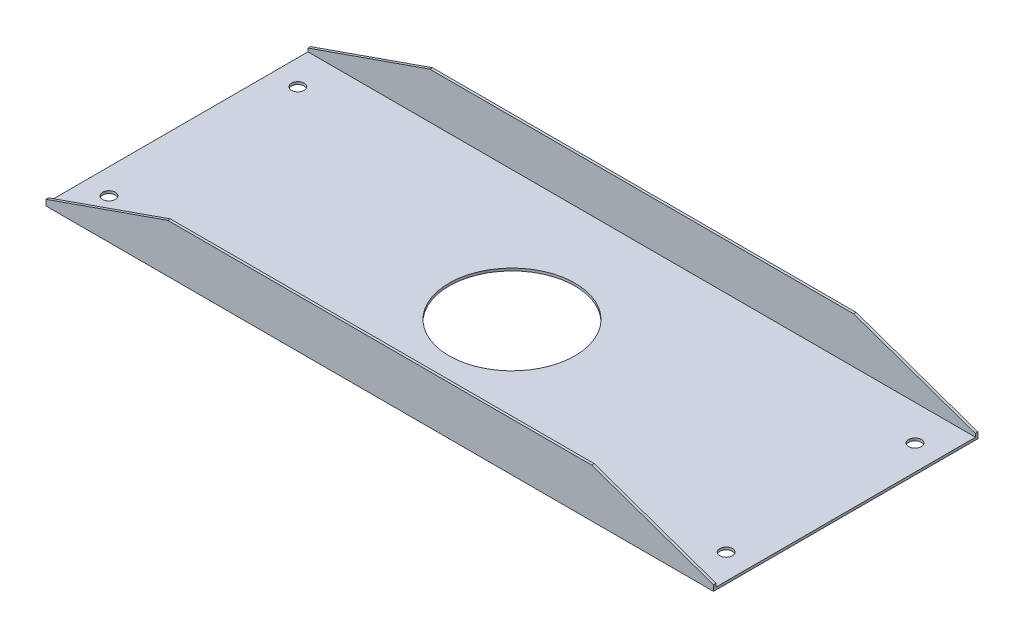
SolidWorks part; units mm, degrees
ref_plane "Спереди" through (0, 0, 0) normal (0, 0, 1) x (1, 0, 0)
ref_plane "Сверху" through (0, 0, 0) normal (0, 1, 0) x (1, 0, 0)
ref_plane "Справа" through (0, 0, 0) normal (1, 0, 0) x (0, 0, -1)
sketch "Эскиз1" plane through (0, 0, 0) normal (1, 0, 0) x (0, 0, -1)
  line L0 (-105, 0) -> (105, 0)
  line L1 (105, 0) -> (105, 38.5)
  line L2 (-105, 0) -> (-105, 38.5)
  dimension "D1" = 210
  dimension "D2" = 38.5
  dimension "D3" = 38.5
extrude "Вытянуть-Тонкостенный1" add sketch "Эскиз1" along normal blind 530 thin thin type one direction wall 2
sketch "Эскиз2" plane through (0, 0, -105) normal (0, 0, -1) x (-1, 0, 0)
  line L0 (-530, 0) -> (-530, 4.6148)
  line L1 (-530, 38.5) -> (-530, 0) construction
  line L2 (-530, 4.6148) -> (-433.2757, 38.5)
  line L3 (-530, 38.5) -> (0, 38.5) construction
  line L4 (-433.2757, 38.5) -> (-96.7243, 38.5)
  line L5 (-96.7243, 38.5) -> (0, 4.6148)
  line L6 (0, 38.5) -> (0, 0) construction
  line L7 (0, 4.6148) -> (0, 0)
  line L8 (0, 0) -> (-530, 0)
extrude "Вырез-Вытянуть2" cut sketch "Эскиз2" against normal through all flip side to cut
sketch "Эскиз3" plane through (0, 2, 0) normal (0, 1, 0) x (1, 0, 0)
  line L0 (20, 115.302) -> (20, -116.3672) construction
  line L1 (0, 103) -> (0, -103) construction
  line L2 (0, 105) -> (96.7243, 105) construction
  line L3 (510, 126.018) -> (510, -161.4271) construction
  line L4 (530, 103) -> (530, -103) construction
  line L5 (0, 103) -> (530, -103) construction
  line L6 (530, 103) -> (0, -103) construction
  circle A0 centre (20, 75) radius 5
  circle A1 centre (20, -75) radius 5
  circle A2 centre (510, 75) radius 5
  circle A3 centre (510, -75) radius 5
  circle A4 centre (265, 0) radius 50
  dimension "D2" = 30
  dimension "D1" = 20
  dimension "D3" = 150
  dimension "D4" = 20
extrude "Вырез-Вытянуть3" cut sketch "Эскиз3" against normal through all
